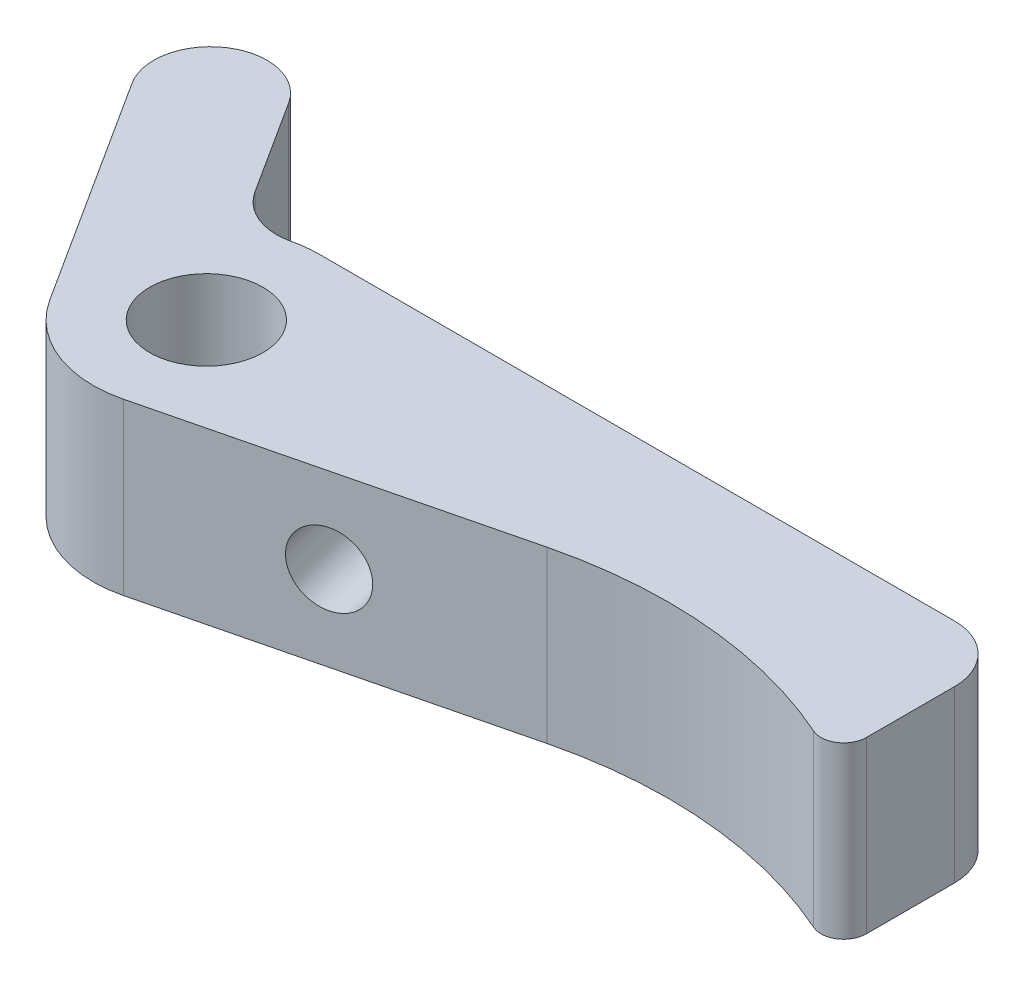
SolidWorks part; units mm, degrees
material "6061-T6 (SS)"
ref_plane "Front" through (0, 0, 0) normal (0, 0, 1) x (1, 0, 0)
ref_plane "Top" through (0, 0, 0) normal (0, 1, 0) x (1, 0, 0)
ref_plane "Right" through (0, 0, 0) normal (1, 0, 0) x (0, 0, -1)
sketch "Sketch1" plane through (0, 0, 0) normal (0, 1, 0) x (1, 0, 0)
  line L0 (0, 6.35) -> (38.735, 6.35)
  line L1 (38.735, 6.35) -> (38.735, -3.81)
  line L2 (1.5172, -6.1661) -> (20.5672, -1.4788)
  line L3 (-3.4246, 5.3474) -> (-9.9315, 15.5074)
  line L4 (-9.9315, 15.5074) -> (-15.2788, 12.0827)
  line L5 (-15.2788, 12.0827) -> (-5.3474, -3.4246)
  circle A0 centre (0, 0) radius 3.175
  circle A1 centre (0, 0) radius 6.35
  arc A2 (20.5672, -1.4788) -> (38.735, -3.81) centre (26.6359, -26.1432) cw
  dimension "D1" = 6.35
  dimension "D2" = 12.7
  dimension "D5" = 19.05
  dimension "D7" = 12.065
  dimension "D6" = 25.4
  dimension "D3" = 38.735
  dimension "D4" = 10.16
  dimension "D8" = 6.35
  dimension "D9" = 10.16
extrude "Boss-Extrude1" add sketch "Sketch1" along normal blind 9.525 contours A1 A0 | L2 A2 L1 L0 A1 | A1 L3 L4 L5 region at (20.9795, 0, -1.9449) region at (4.3631, 0, -4.3631) region at (-9.094, 0, -7.9821)
fillet "Fillet1" radius 3.175 4 edges at (38.735, 4.7625, -6.35) (-3.4246, 4.7625, -5.3474) (-15.2788, 4.7625, -12.0827) (-9.9315, 4.7625, -15.5074)
fillet "Fillet2" radius 1.27 1 edges at (38.735, 4.7625, 3.81)
sketch "Sketch4" plane through (1.5172, 0, 6.1661) normal (0.2389, 0, 0.971) x (0.971, 0, -0.2389)
  line L0 (0, 4.7625) -> (9.525, 4.7625) construction
  line L1 (0, 9.525) -> (0, 0) construction
  point P0 (9.525, 4.7625)
  dimension "D1" = 9.525
hole_wizard "#10-32 Tapped Hole2" positions "Sketch4" profile "Sketch3" tap size "#10-32" standard "ANSI Inch"
sketch "Sketch3" plane through (10.7663, 4.7625, 3.8903) normal (0, 1, 0) x (0.971, 0, -0.2389)
  line L0 (0, 0) -> (0, 8.8333)
  line L1 (0, 8.8333) -> (2.0193, 7.62)
  line L2 (2.0193, 7.62) -> (2.0193, 0)
  line L5 (2.0193, 0) -> (0, 0)
  line L10 (0, 8.8333) -> (-2.0193, 7.62) construction
  line L11 (0, -6.35) -> (0, 107.95) construction
  dimension "Tap Drill Dia." = 4.0386
  dimension "Tap Drill Depth" = 7.62
  dimension "Drill Angle" = 118
cosmetic thread "Hole Thread1" parameters "D1"=9.652, "D2"=4.826
